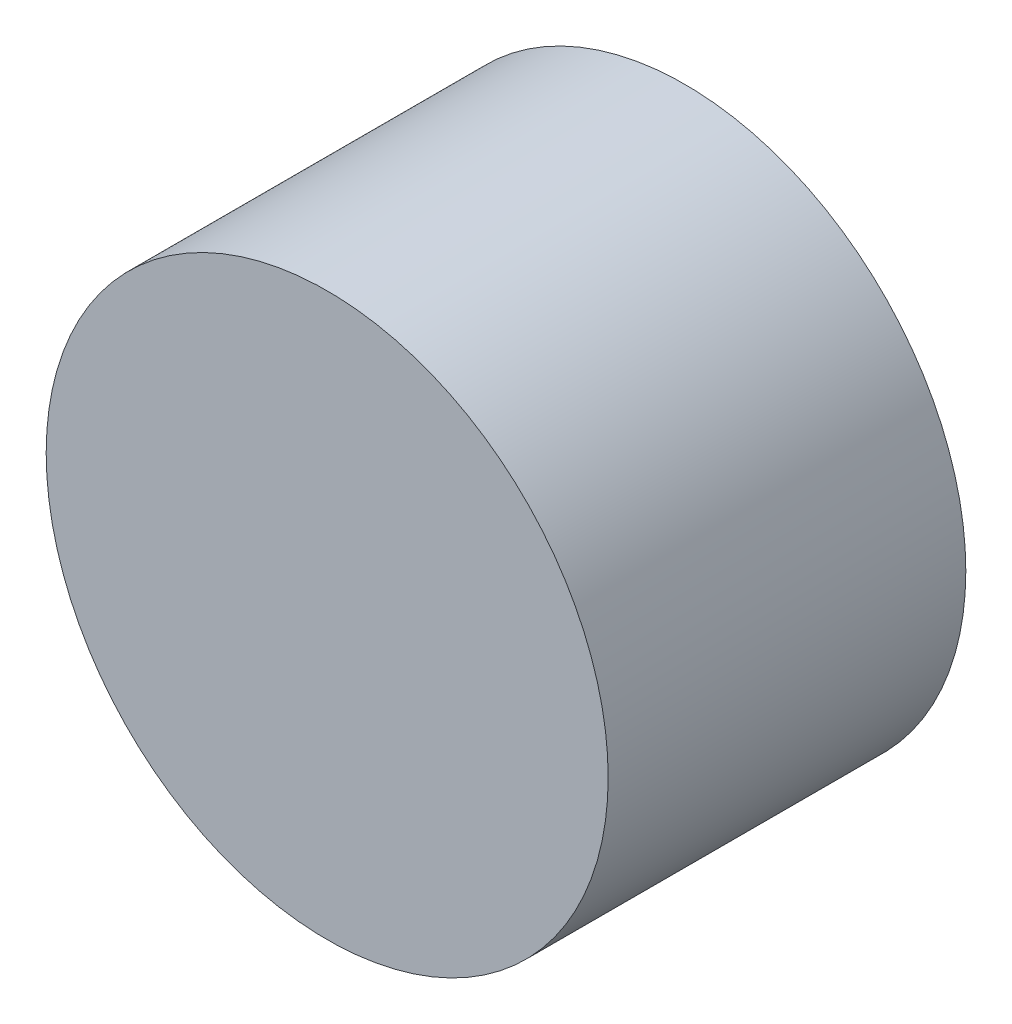
SolidWorks part; units mm, degrees
ref_plane "Front Plane" through (0, 0, 0) normal (0, 0, 1) x (1, 0, 0)
ref_plane "Top Plane" through (0, 0, 0) normal (0, 1, 0) x (1, 0, 0)
ref_plane "Right Plane" through (0, 0, 0) normal (1, 0, 0) x (0, 0, -1)
ref_plane "Plane1" through (0, 0, 1282.3573) normal (0, 0, -1) x (-1, 0, 0)
sketch "Sketch1" plane through (0, 0, 1282.3573) normal (0, 0, -1) x (-1, 0, 0)
  circle A0 centre (-681.387, 902.3682) radius 5.5
  circle A1 centre (-681.387, 902.3682) radius 16.8 construction
  dimension "D1" = 11
extrude "Boss-Extrude1" add sketch "Sketch1" along normal up to surface (7 mm away) contours A0
